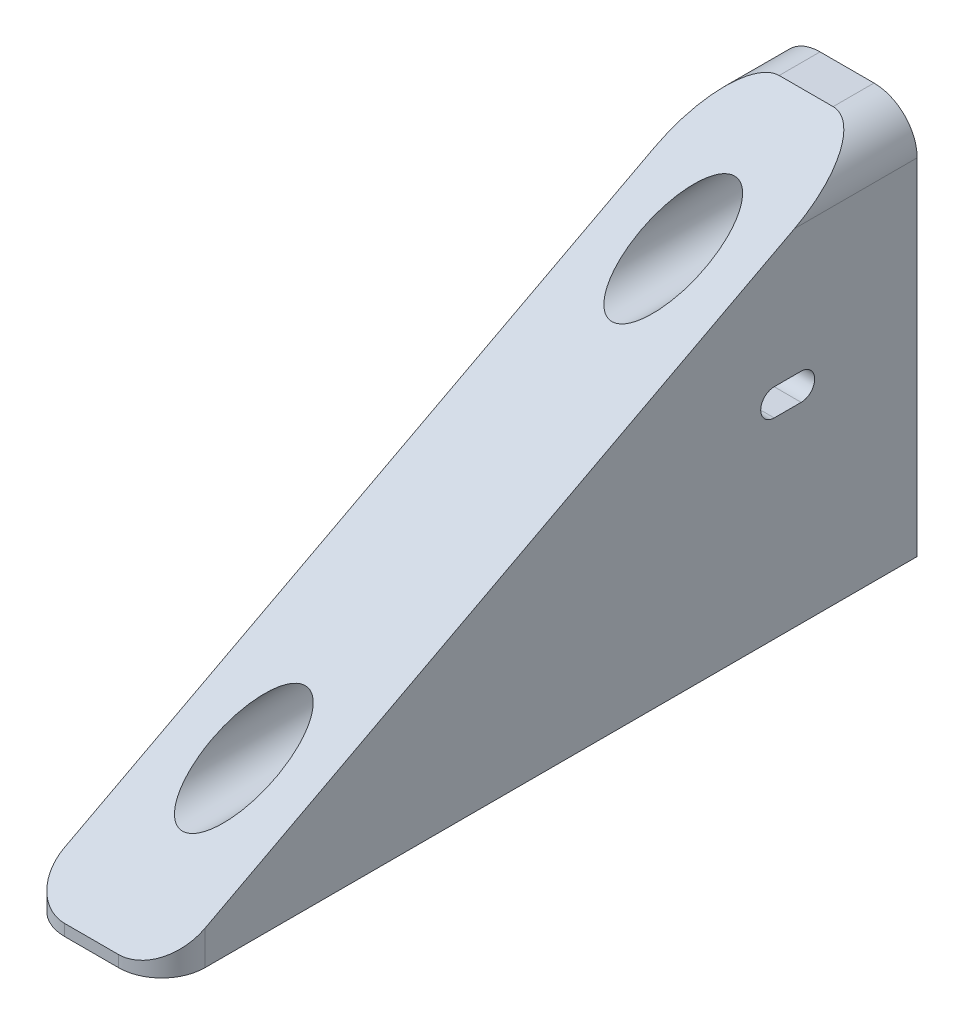
SolidWorks part; units mm, degrees
material "ABS (75% Infill)"
ref_plane "Front" through (0, 0, 0) normal (0, 0, 1) x (1, 0, 0)
ref_plane "Top" through (0, 0, 0) normal (0, 1, 0) x (1, 0, 0)
ref_plane "Right" through (0, 0, 0) normal (1, 0, 0) x (0, 0, -1)
sketch "Sketch1" plane through (0, 0, 0) normal (1, 0, 0) x (0, 0, -1)
  line L0 (0, 19) -> (0, -19)
  line L1 (0, -19) -> (-72, -19)
  line L2 (-72, -19) -> (0, 19)
  dimension "D1" = 38
  dimension "D2" = 72
extrude "Boss-Extrude1" add sketch "Sketch1" along normal mid plane 13
sketch "Sketch2" plane through (0, 0, 0) normal (0, 0, 1) x (1, 0, 0)
  line L0 (50, 0) -> (-50, 0) construction
  circle A0 centre (0, 10.5) radius 1.575
  circle A1 centre (0, 10.5) radius 3
  circle A2 centre (0, -10.5) radius 1.575
  circle A3 centre (0, -10.5) radius 3
  dimension "D1" = 21
  dimension "D2" = 3.15
  dimension "D3" = 6
extrude "Cut-Extrude1" cut sketch "Sketch2" along normal through all contours A0 | A2
extrude "Cut-Extrude2" cut sketch "Sketch2<3>" along normal through all from offset 5 contours A1 | A3
sketch "Sketch2<3>" plane through (0, 0, 0) normal (0, 0, 1) x (1, 0, 0) same geometry as "Sketch2"
sketch "Sketch3" plane through (0, -19, 0) normal (0, -1, 0) x (1, 0, 0)
  line L0 (0, 72) -> (0, 0) construction
  line L1 (6.5, 72) -> (-6.5, 72) construction
  line L2 (-6.5, 3) -> (6.5, 3) construction
  line L3 (-6.5, 72) -> (-6.5, 0) construction
  line L4 (6.5, 72) -> (6.5, 0) construction
  line L5 (6.5, 0) -> (-6.5, 0) construction
  point P5 (0, 15)
  point P6 (0, 43)
  dimension "D1" = 3
  dimension "D2" = 12
  dimension "D3" = 28
sketch "Sketch5" plane through (0, 0, 0) normal (1, 0, 0) x (0, 0, -1)
  line L0 (-13.25, 0) -> (-10.75, 0) construction
  line L1 (-13.25, 1.25) -> (-10.75, 1.25)
  line L2 (-13.25, -1.25) -> (-10.75, -1.25)
  arc A0 (-13.25, 1.25) -> (-13.25, -1.25) centre (-13.25, 0) ccw
  arc A1 (-10.75, -1.25) -> (-10.75, 1.25) centre (-10.75, 0) ccw
  point P2 (-12, 0)
  dimension "D1" = 2.5
  dimension "D2" = 2.5
  dimension "D3" = 12
extrude "Cut-Extrude3" cut sketch "Sketch5" against normal through all both and the other way through all
chamfer "Chamfer1" distance 2 angle 90 2 edges at (0, -19, 72) (0, 19, 0) first distance on face at (0, -19, 36) first distance on face at (-1.575, -10.5, 0)
fillet "Fillet2" radius 4 4 edges at (-6.5, 17, 1.8947) (6.5, 17, 1.8947) (6.5, -18.4722, 70) (-6.5, -18.4722, 70)
